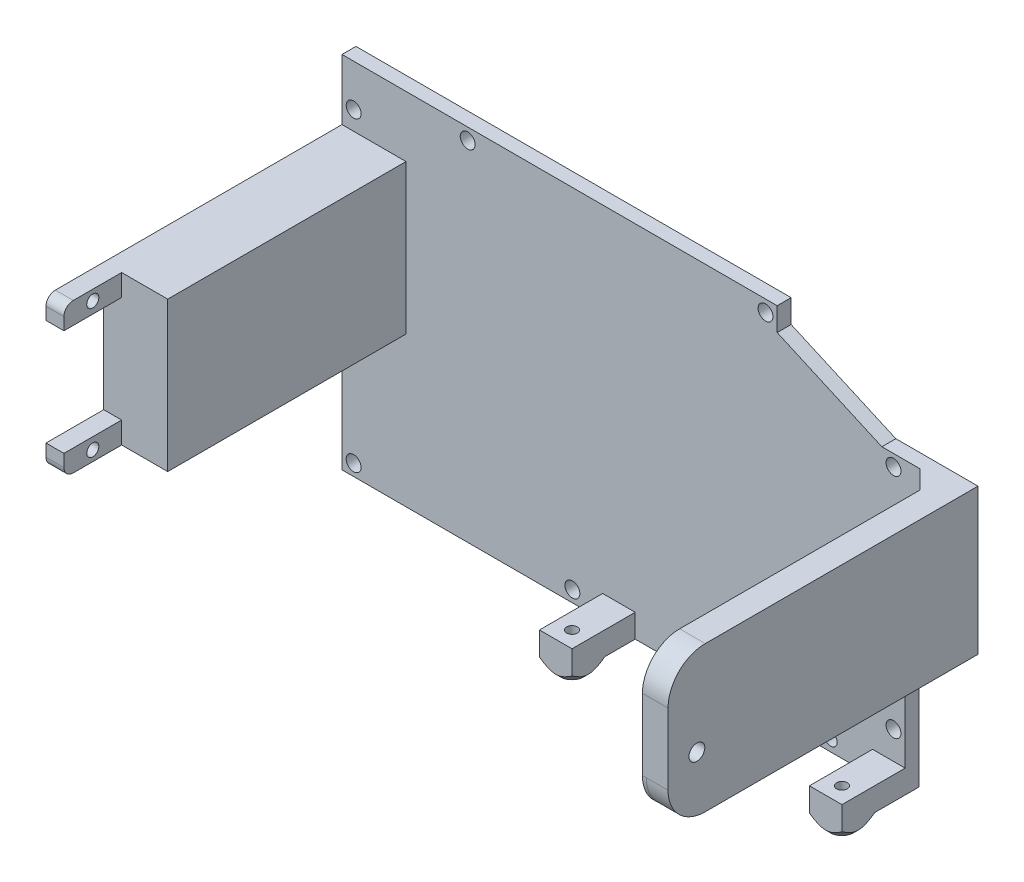
SolidWorks part; units mm, degrees
material "Nylon 101 70%"
ref_plane "Front Plane" through (0, 0, 0) normal (0, 0, 1) x (1, 0, 0)
ref_plane "Top Plane" through (0, 0, 0) normal (0, 1, 0) x (1, 0, 0)
ref_plane "Right Plane" through (0, 0, 0) normal (1, 0, 0) x (0, 0, -1)
sketch "Sketch19" plane through (0, 0, 0) normal (0, 0, 1) x (1, 0, 0)
  line L10 (-54.5, -38) -> (-54.5, 29.3)
  line L11 (56.5, -38) -> (-54.5, -38)
  line L12 (56.5, 19.3) -> (56.5, -38)
  line L13 (61.5, 19.3) -> (56.5, 19.3)
  line L14 (61.5, -43) -> (61.5, 19.3)
  line L15 (-59.5, -43) -> (61.5, -43)
  line L16 (-59.5, 34.3) -> (-59.5, -43)
  line L17 (34, 34.3) -> (-59.5, 34.3)
  line L18 (34, 29.3) -> (34, 34.3)
  line L19 (-54.5, 29.3) -> (34, 29.3)
  line L20 (-54.5, -38) -> (-54.5, 29.3) construction
  line L21 (56.5, -38) -> (-54.5, -38) construction
  line L22 (56.5, 19.3) -> (56.5, -38) construction
  line L23 (61.5, 19.3) -> (56.5, 19.3)
  line L24 (61.5, -43) -> (61.5, 19.3)
  line L25 (-59.5, -43) -> (61.5, -43)
  line L26 (-59.5, 34.3) -> (-59.5, -43)
  line L27 (34, 34.3) -> (-59.5, 34.3)
  line L28 (34, 29.3) -> (34, 34.3)
  line L29 (-54.5, 29.3) -> (34, 29.3) construction
  line L40 (34, 29.3) -> (56.5, 19.3)
  dimension "D1" = 0
extrude "Base" add sketch "Sketch19" along normal blind 3
ref_plane "Top" through (0, 0, 3) normal (0, 0, 1) x (1, 0, 0)
sketch "Sketch20" plane through (0, 0, 0) normal (0, 0, 1) x (1, 0, 0)
  line L0 (-55.6482, 16.7928) -> (-55.6482, 21.05) construction
  line L1 (-55.4482, -7.9314) -> (-55.4482, -9.2765) construction
  line L2 (-55.8482, -6.2) -> (-73.6482, -6.2) construction
  line L3 (-55.8482, -6.2) -> (-73.6482, -6.2) construction
  line L4 (-55.6482, 16.7928) -> (-55.6482, 21.05) construction
  line L5 (-55.4482, -7.9314) -> (-55.4482, -9.2765) construction
  line L6 (-55.8482, 16.6) -> (-73.6482, 16.6) construction
  line L7 (-55.8482, 16.6) -> (-73.6482, 16.6) construction
  line L8 (-55.6482, -10.65) -> (-55.6482, -6.3928) construction
  line L9 (-55.4482, 21.25) -> (-53.2982, 21.25) construction
  line L10 (-55.4482, 18.2177) -> (-55.4482, 19.799) construction
  line L11 (-55.4482, 18.2177) -> (-55.4482, 19.799) construction
  line L12 (-53.2982, -10.85) -> (-55.4482, -10.85) construction
  line L13 (-53.2982, -10.85) -> (-55.4482, -10.85)
  line L14 (-55.4482, 21.25) -> (-53.2982, 21.25)
  line L15 (-51.3482, -6.2) -> (-52.8982, -6.2) construction
  line L16 (-51.3482, -6.2) -> (-52.8982, -6.2) construction
  line L17 (-52.8982, 16.6) -> (-51.3482, 16.6) construction
  line L18 (-52.8982, 16.6) -> (-51.3482, 16.6) construction
  line L19 (-45.7482, 8.6095) -> (-50.9482, 8.6095) construction
  line L20 (-45.7482, 8.6095) -> (-50.9482, 8.6095) construction
  line L21 (-50.9482, -6.2) -> (-45.3482, -6.2) construction
  line L22 (-50.9482, -6.2) -> (-45.3482, -6.2) construction
  line L23 (-53.2982, 21.25) -> (-45.7482, 21.25)
  line L24 (-45.7482, 21.25) -> (-45.7482, 8.6095)
  line L25 (-45.7482, 8.6095) -> (-45.7482, -10.85)
  line L26 (-45.7482, -10.85) -> (-53.2982, -10.85)
  line L27 (-55.4482, 21.25) -> (-59.5, 21.25)
  line L28 (-59.5, 34.3) -> (-59.5, -43) construction
  line L29 (-59.5, 21.25) -> (-59.5, -10.85)
  line L30 (-59.5, -10.85) -> (-55.4482, -10.85)
  line L31 (-55.6482, -10.65) -> (-55.6482, -6.3928) construction
extrude "Servo support" add sketch "Sketch20" along normal up to surface (54.2 mm away)
sketch "Sketch21" plane through (0, 0, 54.2) normal (0, 0, 1) x (1, 0, 0)
  line L4 (-55.8482, -6.2) -> (-73.6482, -6.2) construction
  line L5 (-55.8482, -6.2) -> (-59.5, -6.2)
  line L6 (-55.8482, 16.6) -> (-73.6482, 16.6) construction
  line L7 (-55.8482, 16.6) -> (-59.5, 16.6)
  line L8 (-59.5, -10.85) -> (-55.4482, -10.85) construction
  line L9 (-59.5, -10.85) -> (-55.6482, -10.85)
  line L10 (-55.4482, 21.25) -> (-59.5, 21.25) construction
  line L11 (-55.6482, 21.25) -> (-59.5, 21.25)
  line L15 (-55.6482, 16.6) -> (-55.8482, 16.6)
  line L18 (-55.6482, -6.2) -> (-55.8482, -6.2)
  line L20 (-59.5, 21.25) -> (-59.5, -10.85) construction
  line L21 (-59.5, 21.25) -> (-59.5, 16.6)
  line L22 (-59.5, -6.2) -> (-59.5, -10.85)
  line L23 (-55.6482, 16.7928) -> (-55.6482, 21.05) construction
  line L24 (-55.6482, 16.6) -> (-55.6482, 21.25)
  line L25 (-55.6482, -10.65) -> (-55.6482, -6.3928) construction
  line L26 (-55.6482, -10.85) -> (-55.6482, -6.2)
extrude "Servo mounts" add sketch "Sketch21" along normal up to surface (12.4 mm away)
sketch "Sketch22" plane through (-59.5, 0, 0) normal (-1, 0, 0) x (0, 0, 1)
  arc A0 (60.752, -9.2765) -> (60.048, -9.2765) centre (60.4, -8.65) ccw construction
  arc A1 (60.752, -9.2765) -> (60.048, -9.2765) centre (60.4, -8.65) ccw construction
  arc A2 (60.0372, 19.799) -> (60.7628, 19.799) centre (60.4, 19.05) ccw construction
  arc A3 (60.0372, 19.799) -> (60.7628, 19.799) centre (60.4, 19.05) ccw construction
  circle A4 centre (60.4, -8.65) radius 1.3
  circle A5 centre (60.4, 19.05) radius 1.3
  dimension "D1" = 2.6
extrude "Servo screws" cut sketch "Sketch22" against normal up to next
fillet "Fillet1" radius 2 2 edges at (-57.5741, -10.85, 66.6) (-57.5741, 21.25, 66.6)
sketch "Sketch23" plane through (0, 0, 0) normal (0, 0, 1) x (1, 0, 0)
  line L2 (61.5, -12) -> (74.1518, -12)
  line L3 (61.5, -43) -> (61.5, 19.3) construction
  line L4 (74.1518, -12) -> (74.1518, 19.3)
  line L5 (61.5, 19.3) -> (74.1518, 19.3)
  line L6 (61.5, 19.3) -> (61.5, -12)
  line L7 (68.1518, -1.4) -> (68.1518, 1.4) construction
  line L8 (68.1518, -1.4) -> (68.1518, 1.4) construction
  point P0 (68.1518, 0)
  dimension "D1" = 6
  dimension "D2" = 12
extrude "Shaft support" add sketch "Sketch23" along normal up to surface (3 mm away) up to plane "Top"
sketch "Sketch24" plane through (0, 0, 0) normal (0, 0, 1) x (1, 0, 0)
  line L0 (74.1518, -12) -> (74.1518, 19.3) construction
  line L1 (74.1518, -12) -> (74.1518, 19.3)
  line L2 (61.5, 19.3) -> (74.1518, 19.3) construction
  line L3 (68.6518, 19.3) -> (74.1518, 19.3)
  line L4 (61.5, -12) -> (74.1518, -12) construction
  line L5 (68.6518, -12) -> (74.1518, -12)
  line L6 (68.6518, 19.3) -> (68.6518, -12)
  line L8 (68.1518, -1.4) -> (68.1518, 1.4) construction
  dimension "D1" = 0.5
extrude "Boss-Extrude6" add sketch "Sketch24" along normal up to surface (66.6 mm away) up to face at (-57.5741, -7.525, 66.6)
fillet "Fillet2" radius 8 1 edges at (61.5, -12, 1.5)
fillet "Fillet3" radius 8 3 edges at (71.4018, 19.3, 66.6) (71.8259, -12, 66.6) (69.0753, -12.0113, 66.6)
sketch "Sketch25" plane through (68.6518, 0, 0) normal (-1, 0, 0) x (0, 0, 1)
  circle A0 centre (60.4, 0) radius 1.1 construction
  circle A1 centre (60.4, 0) radius 1.1 construction
  circle A2 centre (60.4, 0) radius 1.7
  dimension "D1" = 3.4
extrude "Shaft" cut sketch "Sketch25" against normal up to next
sketch "Sketch26" plane through (0, 0, 0) normal (0, 0, 1) x (1, 0, 0)
  circle A5 centre (-57, 25.3) radius 1.4
  circle A6 centre (-57, 25.3) radius 1.4 construction
  circle A7 centre (-10, -40.5) radius 1.4
  circle A8 centre (-10, -40.5) radius 1.4 construction
  circle A9 centre (59, -32) radius 1.4
  circle A10 centre (59, -32) radius 1.4 construction
  circle A13 centre (59, 16.8) radius 1.4
  circle A14 centre (59, 16.8) radius 1.4 construction
  circle A15 centre (31.5, 31.8) radius 1.4
  circle A16 centre (31.5, 31.8) radius 1.4 construction
  circle A19 centre (-32.5, 31.8) radius 1.4
  circle A20 centre (-32.5, 31.8) radius 1.4 construction
  circle A21 centre (-57, -40.5) radius 1.4
  circle A22 centre (-57, -40.5) radius 1.4 construction
  circle A44 centre (-57, -40.5) radius 1.6
  circle A46 centre (-10, -40.5) radius 1.6
  circle A47 centre (59, -32) radius 1.6
  circle A49 centre (59, 16.8) radius 1.6
  circle A50 centre (31.5, 31.8) radius 1.6
  circle A52 centre (-32.5, 31.8) radius 1.6
  circle A53 centre (-57, 25.3) radius 1.6
  circle A63 centre (-57, -14.5) radius 1.4 construction
  circle A64 centre (-57, -14.5) radius 1.4
  circle A112 centre (45.5, -40.5) radius 1.4 construction
  circle A113 centre (45.5, -40.5) radius 1.4
  dimension "D2" = 3.2
  dimension "D3" = 0
  dimension "D4" = 0
  dimension "D5" = 0
  dimension "D7" = 0
  dimension "D8" = 0
  dimension "D10" = 0
  dimension "D11" = 0
extrude "Screws" cut sketch "Sketch26" along normal up to next
sketch "Sketch30" plane through (0, -43, 0) normal (0, -1, 0) x (1, 0, 0)
  circle A1 centre (0, 13.0765) radius 1.35
  circle A2 centre (0, 13.0765) radius 1.35 construction
  circle A3 centre (58, 13.0765) radius 1.35
  circle A4 centre (58, 13.0765) radius 1.35 construction
  circle A10 centre (0, 13.0765) radius 2.5
  circle A11 centre (58, 13.0765) radius 2.5
  dimension "D3" = 5
  dimension "D1" = 0
  dimension "D2" = 0
sketch "Sketch31" plane through (0, -43, 0) normal (0, -1, 0) x (1, 0, 0)
  line L0 (-59.5, 3) -> (61.5, 3) construction
  line L1 (-3.5, 3) -> (3.5, 3)
  line L2 (-3.5, 3) -> (-3.5, 16.5765)
  line L3 (-3.5, 16.5765) -> (3.5, 16.5765)
  line L4 (3.5, 16.5765) -> (3.5, 3)
  line L5 (54.5, 3) -> (54.5, 16.5765)
  line L6 (54.5, 16.5765) -> (61.5, 16.5765)
  line L7 (61.5, 3) -> (61.5, 16.5765)
  line L9 (0, 13.0765) -> (0, 16.5765) construction
  line L10 (58, 13.0765) -> (58, 16.5765) construction
  line L11 (54.5, 3) -> (61.5, 3)
  dimension "D1" = 7
  dimension "D2" = 3.5
extrude "Boss-Extrude8" add sketch "Sketch31" against normal blind 5
extrude "Boss-Extrude9" add sketch "Sketch30" along normal blind 2.5
sketch "Sketch32" plane through (0, -38, 0) normal (0, 1, 0) x (1, 0, 0)
  circle A0 centre (0, -13.0765) radius 1.15
  circle A1 centre (58, -13.0765) radius 1.15
  dimension "D1" = 2.3
extrude "Cut-Extrude1" cut sketch "Sketch32" against normal up to next
chamfer "Chamfer1" distance 2.5 angle 45 2 edges at (55.5, -43, 13.0765) (-2.5, -43, 13.0765)
chamfer "Chamfer2" distance 4 angle 45 1 edges at (68.6518, 3.6275, 3)
